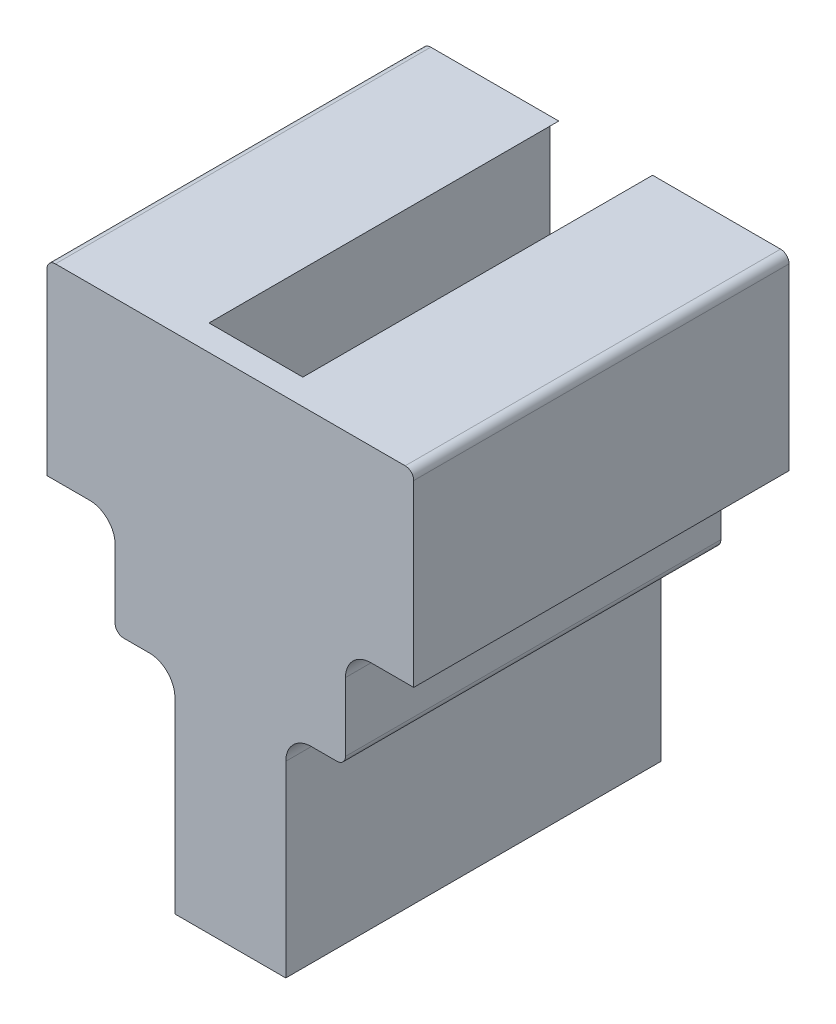
SolidWorks part; units mm, degrees
material "ABS"
ref_plane "Front Plane" through (0, 0, 0) normal (0, 0, 1) x (1, 0, 0)
ref_plane "Top Plane" through (0, 0, 0) normal (0, 1, 0) x (1, 0, 0)
ref_plane "Right Plane" through (0, 0, 0) normal (1, 0, 0) x (0, 0, -1)
sketch "Sketch3" plane through (0, 0, 0) normal (1, 0, 0) x (0, 0, -1)
  line L0 (0, 0) -> (44, 0)
  dimension "D1" = 44
ref_plane "Plane2" through (0, 0, -44) normal (0, 0, -1) x (-1, 0, 0)
sketch "Sketch4" plane through (0, 0, -44) normal (0, 0, -1) x (-1, 0, 0)
  line L0 (-6.5, 0) -> (6.5, 0)
  line L1 (6.5, 0) -> (6.5, 22)
  line L4 (16.5, 37) -> (21.5, 37)
  line L5 (21.5, 37) -> (21.5, 58)
  line L6 (20.5, 59) -> (-20.5, 59)
  line L8 (0, 59) -> (0, 0) construction
  line L9 (-6.5, 0) -> (-6.5, 22)
  line L12 (-16.5, 37) -> (-21.5, 37)
  line L13 (-21.5, 37) -> (-21.5, 58)
  line L15 (-13.5, 34) -> (-13.5, 26)
  line L16 (-12.5, 25) -> (-9.5, 25)
  line L17 (13.5, 34) -> (13.5, 26)
  line L18 (12.5, 25) -> (9.5, 25)
  arc A0 (9.5, 25) -> (6.5, 22) centre (9.5, 22) ccw
  arc A1 (16.5, 37) -> (13.5, 34) centre (16.5, 34) ccw
  arc A2 (-9.5, 25) -> (-6.5, 22) centre (-9.5, 22) cw
  arc A3 (-16.5, 37) -> (-13.5, 34) centre (-16.5, 34) cw
  arc A4 (-13.5, 26) -> (-12.5, 25) centre (-12.5, 26) ccw
  arc A5 (13.5, 26) -> (12.5, 25) centre (12.5, 26) cw
  arc A6 (-20.5, 59) -> (-21.5, 58) centre (-20.5, 58) ccw
  arc A7 (20.5, 59) -> (21.5, 58) centre (20.5, 58) cw
  point P17 (6.5, 25)
  point P20 (13.5, 37)
  point P23 (-6.5, 25)
  point P26 (-13.5, 37)
  point P33 (-21.5, 59)
  point P36 (21.5, 59)
  dimension "D3" = 3
  dimension "D4" = 3
  dimension "D7" = 3
  dimension "D8" = 3
  dimension "D9" = 1
  dimension "D10" = 1
  dimension "D5" = 1
  dimension "D1" = 6.5
  dimension "D2" = 25
  dimension "D6" = 8
sweep "Sweep1" add profiles "Sketch4" path "Sketch3"
sketch "Sketch5" plane through (0, 0, -44) normal (0, 0, -1) x (-1, 0, 0)
  line L0 (0, 0) -> (0, 59) construction
  line L1 (-6.5, 0) -> (6.5, 0) construction
  line L2 (20.5, 59) -> (-20.5, 59) construction
  line L3 (-1, 0) -> (1, 0)
  line L4 (1.5, 0.5) -> (1.5, 20)
  line L5 (1.5, 20) -> (2.5, 20)
  line L6 (3.5, 21) -> (3.5, 26)
  line L7 (4.5, 27) -> (5.5, 27)
  line L8 (6.5, 28) -> (6.5, 58)
  line L9 (5.5, 59) -> (-5.5, 59)
  line L11 (-6.5, 28) -> (-6.5, 58)
  line L12 (-4.5, 27) -> (-5.5, 27)
  line L13 (-3.5, 21) -> (-3.5, 26)
  line L14 (-1.5, 20) -> (-2.5, 20)
  line L15 (-1.5, 0.5) -> (-1.5, 20)
  arc A0 (-5.5, 59) -> (-6.5, 58) centre (-5.5, 58) ccw
  arc A1 (5.5, 59) -> (6.5, 58) centre (5.5, 58) cw
  arc A2 (6.5, 28) -> (5.5, 27) centre (5.5, 28) cw
  arc A3 (-6.5, 28) -> (-5.5, 27) centre (-5.5, 28) ccw
  arc A4 (-3.5, 21) -> (-2.5, 20) centre (-2.5, 21) ccw
  arc A5 (3.5, 21) -> (2.5, 20) centre (2.5, 21) cw
  arc A6 (-4.5, 27) -> (-3.5, 26) centre (-4.5, 26) cw
  arc A7 (4.5, 27) -> (3.5, 26) centre (4.5, 26) ccw
  arc A8 (-1, 0) -> (-1.5, 0.5) centre (-1, 0.5) cw
  arc A9 (1, 0) -> (1.5, 0.5) centre (1, 0.5) ccw
  point P22 (6.5, 59)
  point P25 (6.5, 27)
  point P32 (3.5, 20)
  point P37 (3.5, 27)
  point P42 (1.5, 0)
  dimension "D8" = 1
  dimension "D9" = 1
  dimension "D10" = 1
  dimension "D11" = 1
  dimension "D12" = 1
  dimension "D13" = 1
  dimension "D14" = 1
  dimension "D15" = 0.5
  dimension "D16" = 0.5
  dimension "D1" = 1.5
  dimension "D2" = 20
  dimension "D3" = 2
  dimension "D4" = 7
  dimension "D5" = 3
  dimension "D6" = 32
  dimension "D7" = 6.5
extrude "Cut-Extrude1" cut sketch "Sketch5" against normal blind 41 contours L9 A0 L11 A3 L12 A6 L13 A4 L14 L15 A8 L3 A9 L4 L5 A5 L6 A7 L7 A2 L8 A1
